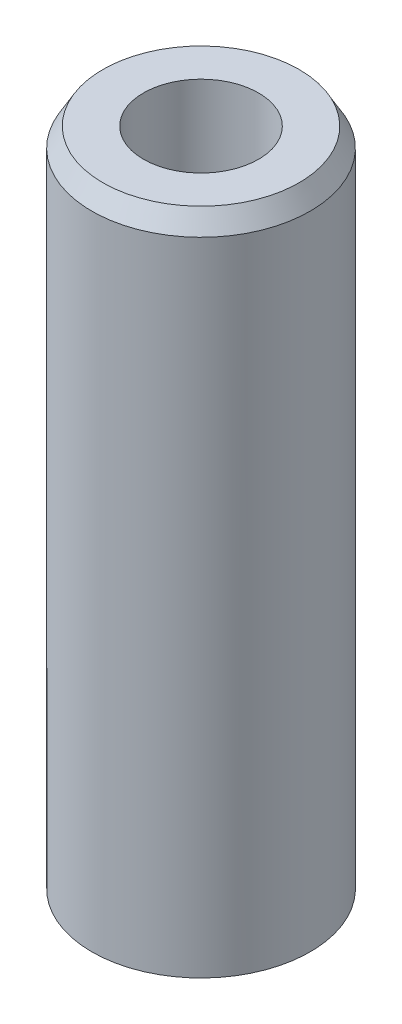
SolidWorks part; units mm, degrees
ref_plane "Front Plane" through (0, 0, 0) normal (0, 0, 1) x (1, 0, 0)
ref_plane "Top Plane" through (0, 0, 0) normal (0, 1, 0) x (1, 0, 0)
ref_plane "Right Plane" through (0, 0, 0) normal (1, 0, 0) x (0, 0, -1)
sketch "Sketch1" plane through (0, 0, 0) normal (0, 1, 0) x (1, 0, 0)
  circle A0 centre (0, 0) radius 17.5
  dimension "SHAFT_OD" = 35
extrude "Boss-Extrude1" add sketch "Sketch1" along normal blind 107.6567
sketch "Sketch2" plane through (0, 0, 0) normal (0, 1, 0) x (1, 0, 0)
  circle A0 centre (0, 0) radius 9.2208
  dimension "BORE_D" = 18.4415
extrude "Cut-Extrude1" cut sketch "Sketch2" along normal through all
chamfer "Chamfer1" distance 3.0629 angle 30 2 edges at (0, 107.6567, 17.5) (0, 0, 17.5) first distance on face at (0, 107.6567, 17.5) first distance on face at (0, 0, 9.2208)
